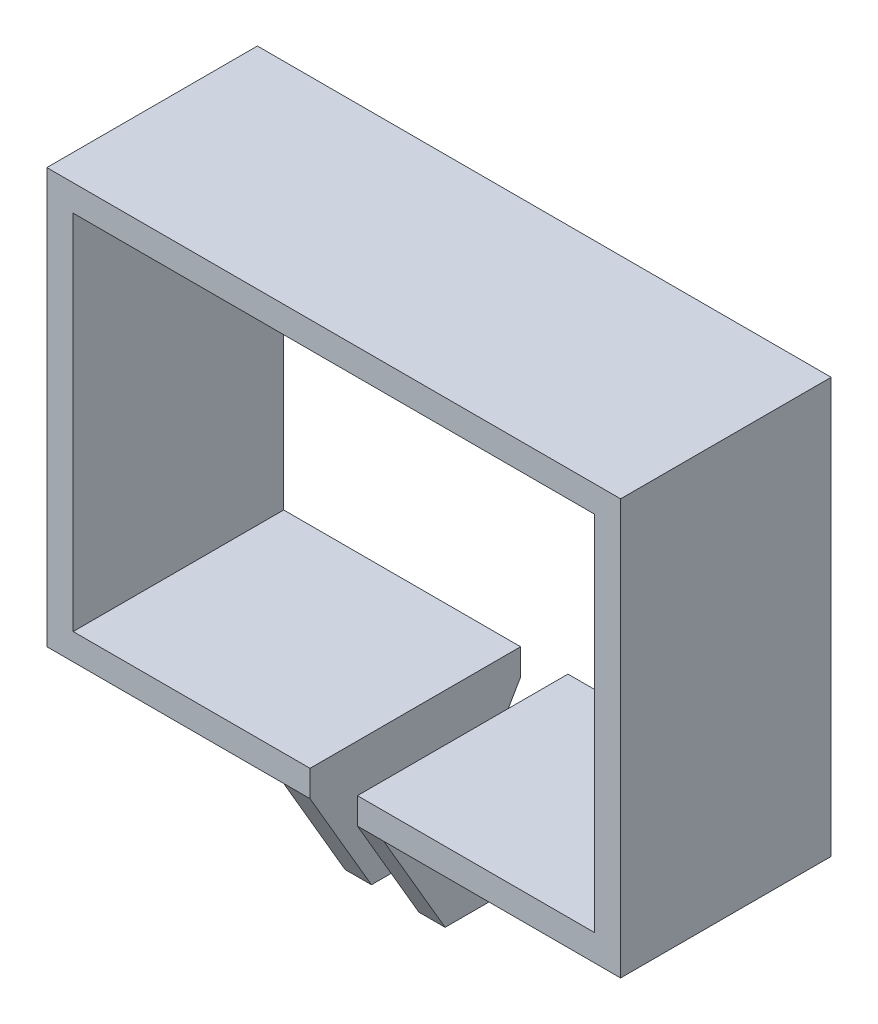
SolidWorks part; units mm, degrees
ref_plane "Plan de face" through (0, 0, 0) normal (0, 0, 1) x (1, 0, 0)
ref_plane "Plan de dessus" through (0, 0, 0) normal (0, 1, 0) x (1, 0, 0)
ref_plane "Plan de droite" through (0, 0, 0) normal (1, 0, 0) x (0, 0, -1)
sketch "Esquisse1" plane through (0, 0, 0) normal (0, 0, 1) x (1, 0, 0)
  line L0 (-29.7, -20.65) -> (-29.7, 20.65)
  line L1 (-29.7, 20.65) -> (29.7, 20.65)
  line L2 (29.7, 20.65) -> (29.7, -20.65)
  line L3 (29.7, -20.65) -> (2.7, -20.65)
  line L4 (2.7, -20.65) -> (2.7, -35.65)
  line L5 (-29.7, -20.65) -> (-2.7, -20.65)
  line L6 (-2.7, -20.65) -> (-2.7, -35.65)
  line L7 (-29.7, 20.65) -> (29.7, -20.65) construction
  dimension "D1" = 59.4
  dimension "D2" = 41.3
  dimension "D3" = 15
  dimension "D4" = 15
  dimension "D5" = 27
  dimension "D6" = 27
extrude "Extru.-Mince1" add sketch "Esquisse1" along normal blind 24 thin thin type one direction wall 3
sketch "Esquisse2" plane through (-5.7, 0, 0) normal (-1, 0, 0) x (0, 0, 1)
  line L0 (0, -23.65) -> (7, -35.65)
  line L1 (24, -35.65) -> (0, -35.65) construction
  line L2 (7, -35.65) -> (0, -35.65)
  line L3 (0, -35.65) -> (0, -23.65)
  line L4 (17, -35.65) -> (24, -35.65)
  line L5 (24, -35.65) -> (24, -23.65)
  line L6 (24, -23.65) -> (17, -35.65)
  circle A0 centre (12, -30.65) radius 2.25
  point P16 (12.4633, -35.65)
  dimension "D5" = 4.5
  dimension "D1" = 7
  dimension "D2" = 7
  dimension "D3" = 12
  dimension "D4" = 5
extrude "Enlèv. mat.-Extru.1" cut sketch "Esquisse2" against normal blind 20
